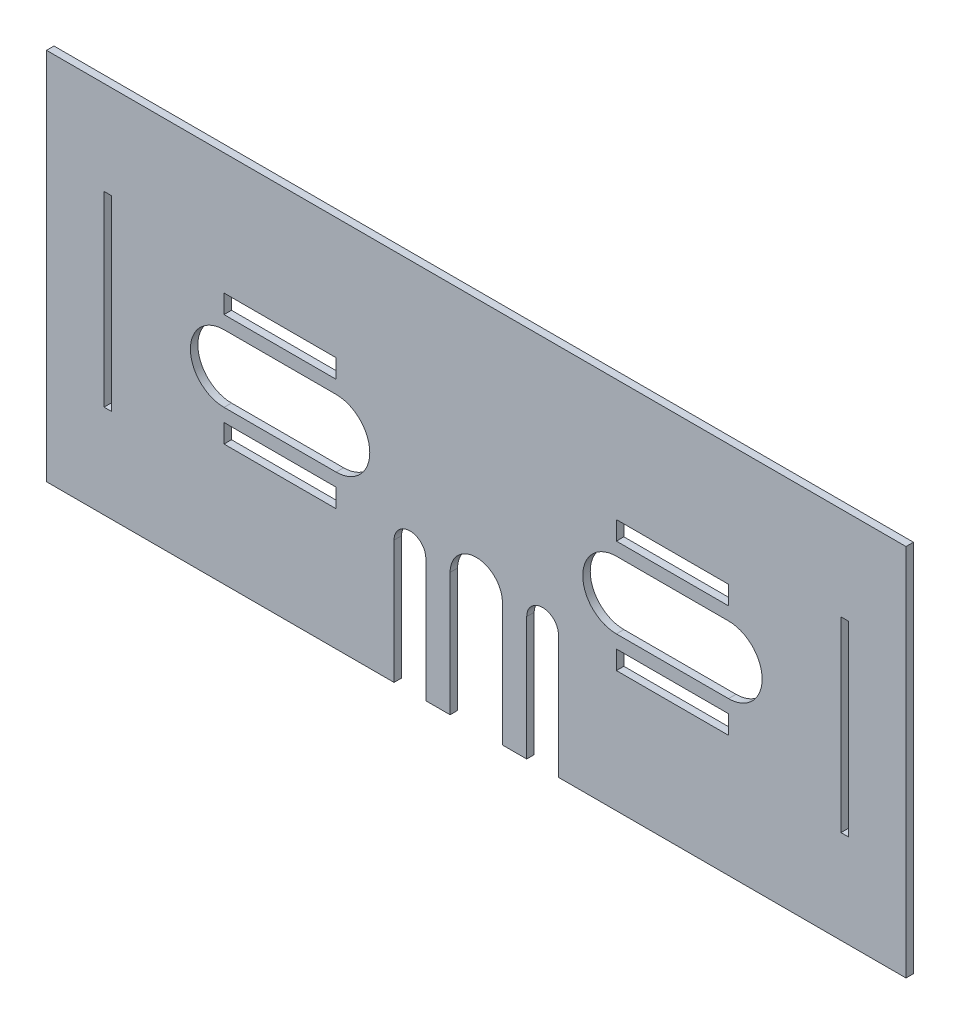
SolidWorks part; units mm, degrees
ref_plane "前视基准面" through (0, 0, 0) normal (0, 0, 1) x (1, 0, 0)
ref_plane "上视基准面" through (0, 0, 0) normal (0, 1, 0) x (1, 0, 0)
ref_plane "右视基准面" through (0, 0, 0) normal (1, 0, 0) x (0, 0, -1)
sketch "草图1" plane through (0, 0, 0) normal (0, 0, 1) x (1, 0, 0)
  line L1 (-49.0448, 20.924) -> (180.9552, 20.924)
  line L2 (-49.0448, 20.924) -> (-49.0448, -79.076)
  line L3 (-49.0448, -79.076) -> (180.9552, -79.076)
  line L4 (180.9552, 20.924) -> (180.9552, -79.076)
  dimension "D1" = 100
  dimension "D2" = 230
extrude "凸台-拉伸1" add sketch "草图1" along normal blind 2
sketch "草图3" plane through (0, 0, 0) normal (0, 0, 1) x (1, 0, 0)
  line L0 (-49.0448, 20.924) -> (-49.0448, -79.076) construction
  line L1 (-33.6448, -4.076) -> (-31.6448, -4.076)
  line L2 (-33.6448, -4.076) -> (-33.6448, -54.076)
  line L3 (-33.6448, -54.076) -> (-31.6448, -54.076)
  line L4 (-31.6448, -4.076) -> (-31.6448, -54.076)
  line L5 (-32.6448, -54.076) -> (-32.6448, -4.076) construction
  line L6 (-33.6448, -29.076) -> (-31.6448, -29.076) construction
  line L7 (180.9552, 20.924) -> (-49.0448, 20.924) construction
  line L8 (65.9552, 82.5756) -> (65.9552, 20.924) construction
  line L9 (65.9552, 20.924) -> (65.9552, -17.9618) construction
  line L10 (-56.6463, -29.076) -> (16.0347, -29.076) construction
  line L11 (16.0347, -29.076) -> (128.3085, -29.076) construction
  line L12 (-1.5448, -44.076) -> (28.4552, -44.076) construction
  line L13 (-1.5448, -11.576) -> (28.4552, -11.576)
  line L14 (-1.5448, -11.576) -> (-1.5448, -16.576)
  line L15 (-1.5448, -16.576) -> (28.4552, -16.576)
  line L16 (28.4552, -11.576) -> (28.4552, -16.576)
  line L17 (13.4552, -16.576) -> (13.4552, -11.576) construction
  line L18 (-1.5448, -14.076) -> (28.4552, -14.076) construction
  line L19 (-1.5448, -20.076) -> (28.4552, -20.076)
  line L21 (-1.5448, -38.076) -> (28.4552, -38.076)
  line L23 (13.4552, -38.076) -> (13.4552, -20.076) construction
  line L24 (-10.6742, -29.076) -> (32.0973, -29.076) construction
  line L25 (13.4552, -41.576) -> (13.4552, -46.576) construction
  line L26 (28.4552, -46.576) -> (28.4552, -41.576)
  line L27 (-1.5448, -41.576) -> (28.4552, -41.576)
  line L28 (-1.5448, -46.576) -> (-1.5448, -41.576)
  line L29 (-1.5448, -46.576) -> (28.4552, -46.576)
  line L30 (118.4552, -41.576) -> (118.4552, -46.576) construction
  line L31 (142.5847, -29.076) -> (99.8132, -29.076) construction
  line L32 (118.4552, -38.076) -> (118.4552, -20.076) construction
  line L33 (133.4552, -14.076) -> (103.4552, -14.076) construction
  line L34 (118.4552, -16.576) -> (118.4552, -11.576) construction
  line L35 (133.4552, -44.076) -> (103.4552, -44.076) construction
  line L36 (165.5552, -29.076) -> (163.5552, -29.076) construction
  line L37 (164.5552, -54.076) -> (164.5552, -4.076) construction
  line L38 (133.4552, -46.576) -> (103.4552, -46.576)
  line L39 (133.4552, -46.576) -> (133.4552, -41.576)
  line L40 (133.4552, -41.576) -> (103.4552, -41.576)
  line L41 (103.4552, -46.576) -> (103.4552, -41.576)
  line L42 (133.4552, -38.076) -> (103.4552, -38.076)
  line L43 (133.4552, -20.076) -> (103.4552, -20.076)
  line L44 (103.4552, -11.576) -> (103.4552, -16.576)
  line L45 (133.4552, -16.576) -> (103.4552, -16.576)
  line L46 (133.4552, -11.576) -> (133.4552, -16.576)
  line L47 (133.4552, -11.576) -> (103.4552, -11.576)
  line L48 (163.5552, -4.076) -> (163.5552, -54.076)
  line L49 (165.5552, -54.076) -> (163.5552, -54.076)
  line L50 (165.5552, -4.076) -> (165.5552, -54.076)
  line L51 (165.5552, -4.076) -> (163.5552, -4.076)
  arc A0 (28.4552, -20.076) -> (28.4552, -38.076) centre (28.4552, -29.076) cw
  arc A1 (-1.5448, -20.076) -> (-1.5448, -38.076) centre (-1.5448, -29.076) ccw
  arc A2 (133.4552, -20.076) -> (133.4552, -38.076) centre (133.4552, -29.076) cw
  arc A3 (103.4552, -20.076) -> (103.4552, -38.076) centre (103.4552, -29.076) ccw
  point P26 (0, 0)
  point P27 (0, 0)
  point P28 (0, 0)
  point P30 (0, 0)
  point P38 (13.4552, -44.076)
  point P73 (118.4552, -29.076)
  point P74 (164.5552, -29.076)
  point P75 (118.4552, -14.076)
  point P76 (118.4552, -44.076)
  point P165 (13.4552, -14.076)
  point P364 (-32.6448, -29.076)
  point P526 (13.4552, -29.076)
  dimension "D9" = 9
  dimension "D10" = 9
  dimension "D1" = 15.4
  dimension "D2" = 25
  dimension "D3" = 50
  dimension "D4" = 2
  dimension "D5" = 12.5
  dimension "D6" = 5
  dimension "D7" = 37.5
  dimension "D8" = 30
  dimension "D11" = 30
  dimension "D12" = 18
  dimension "D13" = 37.5
extrude "切除-拉伸2" cut sketch "草图3" against normal blind 2 and the other way blind 2
sketch "草图4" plane through (0, 0, 0) normal (0, 0, 1) x (1, 0, 0)
  line L0 (-49.0448, -79.076) -> (180.9552, -79.076) construction
  line L2 (43.9552, -46.076) -> (43.9552, -79.076)
  line L3 (43.9552, -79.076) -> (52.4552, -79.076)
  line L4 (52.4552, -46.076) -> (52.4552, -79.076)
  line L5 (48.2052, -79.076) -> (48.2052, -46.076) construction
  line L6 (43.9552, -62.576) -> (52.4552, -62.576) construction
  line L7 (65.9552, 49.5064) -> (65.9552, -10.9661) construction
  line L8 (87.9552, -62.576) -> (79.4552, -62.576) construction
  line L9 (180.9552, 20.924) -> (-49.0448, 20.924) construction
  line L12 (58.9552, -46.076) -> (58.9552, -79.076)
  line L13 (58.9552, -79.076) -> (72.9552, -79.076)
  line L14 (72.9552, -46.076) -> (72.9552, -79.076)
  line L15 (65.9552, -79.076) -> (65.9552, -46.076) construction
  line L16 (58.9552, -62.576) -> (72.9552, -62.576) construction
  line L17 (83.7052, -79.076) -> (83.7052, -46.076) construction
  line L18 (79.4552, -46.076) -> (79.4552, -79.076)
  line L19 (87.9552, -79.076) -> (79.4552, -79.076)
  line L20 (87.9552, -46.076) -> (87.9552, -79.076)
  arc A0 (43.9552, -46.076) -> (52.4552, -46.076) centre (48.2052, -46.076) cw
  arc A1 (58.9552, -46.076) -> (72.9552, -46.076) centre (65.9552, -46.076) cw
  arc A2 (87.9552, -46.076) -> (79.4552, -46.076) centre (83.7052, -46.076) ccw
  point P11 (65.9552, 20.924)
  point P27 (83.7052, -62.576)
  point P155 (65.9552, -62.576)
  point P332 (48.2052, -62.576)
  dimension "D5" = 4.25
  dimension "D6" = 7
  dimension "D1" = 33
  dimension "D2" = 8.5
  dimension "D3" = 6.5
  dimension "D4" = 14
  dimension "D7" = 33
extrude "切除-拉伸3" cut sketch "草图4" against normal blind 2 and the other way blind 2
